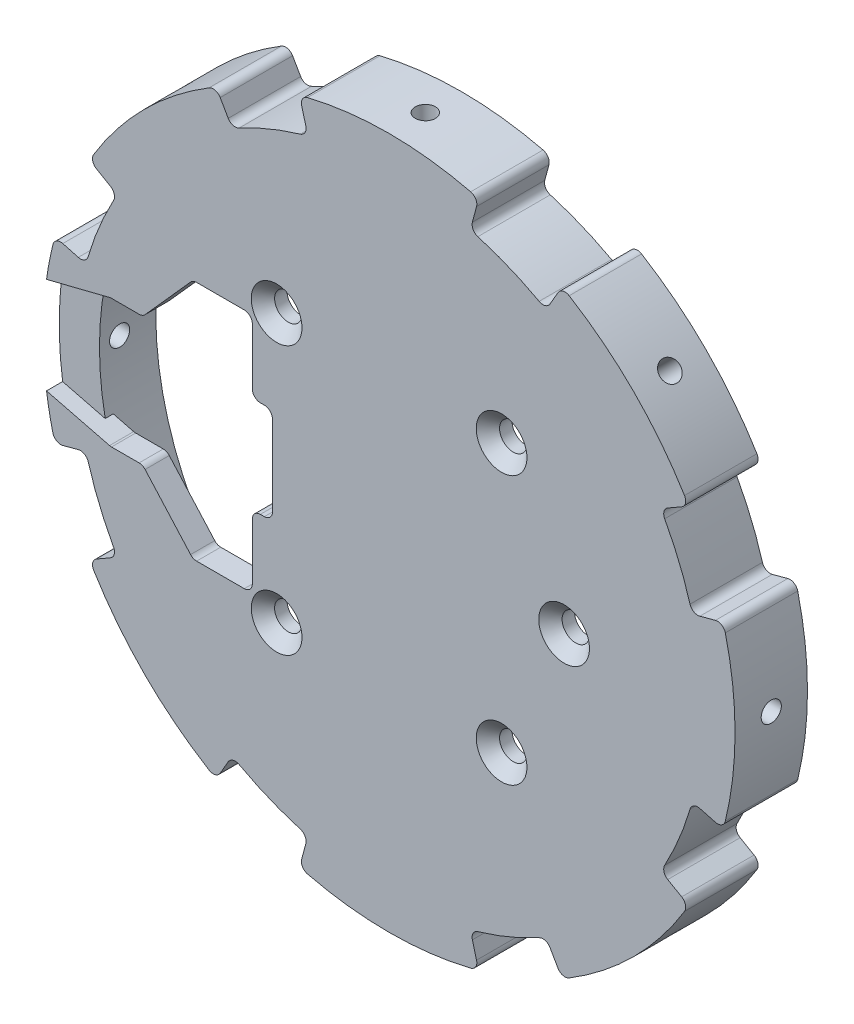
SolidWorks part; units mm, degrees
ref_plane "前视基准面" through (0, 0, 0) normal (0, 0, 1) x (1, 0, 0)
ref_plane "上视基准面" through (0, 0, 0) normal (0, 1, 0) x (1, 0, 0)
ref_plane "右视基准面" through (0, 0, 0) normal (1, 0, 0) x (0, 0, -1)
sketch "草图1" plane through (0, 0, 0) normal (0, 0, 1) x (1, 0, 0)
  line L16 (21.5, 37.2391) -> (19.5, 33.775)
  line L17 (11.1292, 41.5348) -> (10.0939, 37.6711)
  line L18 (-11.1292, 41.5348) -> (-10.0939, 37.6711)
  line L19 (37.2391, 21.5) -> (33.775, 19.5)
  line L20 (41.5348, 11.1292) -> (37.6711, 10.0939)
  line L21 (41.5348, -11.1292) -> (37.6711, -10.0939)
  line L22 (37.2391, -21.5) -> (33.775, -19.5)
  line L23 (21.5, -37.2391) -> (19.5, -33.775)
  line L24 (11.1292, -41.5348) -> (10.0939, -37.6711)
  line L25 (-11.1292, -41.5348) -> (-10.0939, -37.6711)
  line L26 (-21.5, -37.2391) -> (-19.5, -33.775)
  line L27 (-37.2391, -21.5) -> (-33.775, -19.5)
  line L28 (-41.5348, -11.1292) -> (-37.6711, -10.0939)
  line L29 (-41.5348, 11.1292) -> (-37.6711, 10.0939)
  line L30 (-37.2391, 21.5) -> (-33.775, 19.5)
  line L31 (-21.5, 37.2391) -> (-19.5, 33.775)
  circle A1 centre (0, 0) radius 38
  arc A6 (0, 43) -> (-11.1292, 41.5348) centre (0, 0) ccw
  arc A31 (0, 43) -> (11.1292, 41.5348) centre (0, 0) cw
  arc A32 (10.0939, 37.6711) -> (19.5, 33.775) centre (0, 0) cw
  arc A33 (30.4056, 30.4056) -> (21.5, 37.2391) centre (0, 0) ccw
  arc A34 (30.4056, 30.4056) -> (37.2391, 21.5) centre (0, 0) cw
  arc A35 (33.775, 19.5) -> (37.6711, 10.0939) centre (0, 0) cw
  arc A36 (43, 0) -> (41.5348, 11.1292) centre (0, 0) ccw
  arc A37 (43, 0) -> (41.5348, -11.1292) centre (0, 0) cw
  arc A38 (37.6711, -10.0939) -> (33.775, -19.5) centre (0, 0) cw
  arc A39 (30.4056, -30.4056) -> (37.2391, -21.5) centre (0, 0) ccw
  arc A40 (30.4056, -30.4056) -> (21.5, -37.2391) centre (0, 0) cw
  arc A41 (19.5, -33.775) -> (10.0939, -37.6711) centre (0, 0) cw
  arc A42 (0, -43) -> (11.1292, -41.5348) centre (0, 0) ccw
  arc A43 (0, -43) -> (-11.1292, -41.5348) centre (0, 0) cw
  arc A44 (-10.0939, -37.6711) -> (-19.5, -33.775) centre (0, 0) cw
  arc A45 (-30.4056, -30.4056) -> (-21.5, -37.2391) centre (0, 0) ccw
  arc A46 (-30.4056, -30.4056) -> (-37.2391, -21.5) centre (0, 0) cw
  arc A47 (-33.775, -19.5) -> (-37.6711, -10.0939) centre (0, 0) cw
  arc A48 (-43, 0) -> (-41.5348, -11.1292) centre (0, 0) ccw
  arc A49 (-43, 0) -> (-41.5348, 11.1292) centre (0, 0) cw
  arc A50 (-37.6711, 10.0939) -> (-33.775, 19.5) centre (0, 0) cw
  arc A51 (-30.4056, 30.4056) -> (-37.2391, 21.5) centre (0, 0) ccw
  arc A52 (-30.4056, 30.4056) -> (-21.5, 37.2391) centre (0, 0) cw
  arc A53 (-19.5, 33.775) -> (-10.0939, 37.6711) centre (0, 0) cw
  point P55 (0, 0)
  point P56 (0, 0)
  dimension "D1" = 8
extrude "凸台-拉伸1" add sketch "草图1" against normal blind 6
sketch "草图2" plane through (0, 0, 0) normal (0, 0, 1) x (1, 0, 0)
  line L16 (-11.1292, 41.5348) -> (-10.0939, 37.6711)
  line L17 (10.0939, 37.6711) -> (11.1292, 41.5348)
  line L18 (21.5, 37.2391) -> (19.5, 33.775)
  line L19 (33.775, 19.5) -> (37.2391, 21.5)
  line L20 (41.5348, 11.1292) -> (37.6711, 10.0939)
  line L21 (37.6711, -10.0939) -> (41.5348, -11.1292)
  line L22 (37.2391, -21.5) -> (33.775, -19.5)
  line L23 (19.5, -33.775) -> (21.5, -37.2391)
  line L24 (11.1292, -41.5348) -> (10.0939, -37.6711)
  line L25 (-10.0939, -37.6711) -> (-11.1292, -41.5348)
  line L26 (-21.5, -37.2391) -> (-19.5, -33.775)
  line L27 (-33.775, -19.5) -> (-37.2391, -21.5)
  line L28 (-41.5348, -11.1292) -> (-37.6711, -10.0939)
  line L29 (-37.6711, 10.0939) -> (-41.5348, 11.1292)
  line L30 (-37.2391, 21.5) -> (-33.775, 19.5)
  line L31 (-19.5, 33.775) -> (-21.5, 37.2391)
  arc A27 (0, 43) -> (11.1292, 41.5348) centre (0, 0) cw
  arc A28 (10.0939, 37.6711) -> (19.5, 33.775) centre (0, 0) cw
  arc A29 (0, 43) -> (-11.1292, 41.5348) centre (0, 0) ccw
  arc A30 (30.4056, 30.4056) -> (21.5, 37.2391) centre (0, 0) ccw
  arc A31 (30.4056, 30.4056) -> (37.2391, 21.5) centre (0, 0) cw
  arc A32 (33.775, 19.5) -> (37.6711, 10.0939) centre (0, 0) cw
  arc A33 (43, 0) -> (41.5348, 11.1292) centre (0, 0) ccw
  arc A34 (43, 0) -> (41.5348, -11.1292) centre (0, 0) cw
  arc A35 (37.6711, -10.0939) -> (33.775, -19.5) centre (0, 0) cw
  arc A36 (30.4056, -30.4056) -> (37.2391, -21.5) centre (0, 0) ccw
  arc A37 (30.4056, -30.4056) -> (21.5, -37.2391) centre (0, 0) cw
  arc A38 (19.5, -33.775) -> (10.0939, -37.6711) centre (0, 0) cw
  arc A39 (0, -43) -> (11.1292, -41.5348) centre (0, 0) ccw
  arc A40 (0, -43) -> (-11.1292, -41.5348) centre (0, 0) cw
  arc A41 (-10.0939, -37.6711) -> (-19.5, -33.775) centre (0, 0) cw
  arc A42 (-30.4056, -30.4056) -> (-21.5, -37.2391) centre (0, 0) ccw
  arc A43 (-30.4056, -30.4056) -> (-37.2391, -21.5) centre (0, 0) cw
  arc A44 (-33.775, -19.5) -> (-37.6711, -10.0939) centre (0, 0) cw
  arc A45 (-43, 0) -> (-41.5348, -11.1292) centre (0, 0) ccw
  arc A46 (-43, 0) -> (-41.5348, 11.1292) centre (0, 0) cw
  arc A47 (-37.6711, 10.0939) -> (-33.775, 19.5) centre (0, 0) cw
  arc A48 (-30.4056, 30.4056) -> (-37.2391, 21.5) centre (0, 0) ccw
  arc A49 (-30.4056, 30.4056) -> (-21.5, 37.2391) centre (0, 0) cw
  arc A50 (-19.5, 33.775) -> (-10.0939, 37.6711) centre (0, 0) cw
  point P43 (0, 0)
extrude "凸台-拉伸2" add sketch "草图2" along normal blind 3
hole_wizard "M3 锥坑平头的锥孔1" positions "3D草图2" profile "草图4" countersink size "M3" standard "BSI" end condition through all
sketch3d "3D草图2"
  point P25 (13.9806, -16.6615, 3)
  point P27 (21.75, 0, 3)
  point P40 (13.9806, 16.6615, 3)
  point P41 (-13.9806, -16.6615, 3)
  point P42 (-21.75, 0, 3)
  point P43 (-13.9806, 16.6615, 3)
sketch "草图4" plane through (13.9806, -16.6615, 3) normal (1, 0, 0) x (0, -1, 0)
  line L0 (0, 0) -> (0, 9)
  line L1 (0, 9) -> (1.7, 9)
  line L2 (1.7, 9) -> (1.7, 1.45)
  line L3 (1.7, 1.45) -> (3.15, 0)
  line L5 (3.15, 0) -> (0, 0)
  line L6 (-1.7, 1.45) -> (-3.15, 0) construction
  line L11 (0, -6.35) -> (0, 107.95) construction
  dimension "通孔孔直径" = 3.4
  dimension "通孔孔深度" = 9
  dimension "近端锥形沉头孔直径" = 6.3
  dimension "近端锥形沉头孔角度" = 90
hole_wizard "M3x0.5 螺纹孔1" positions "3D草图3" profile "草图5" tap size "M3x0.5" standard "BSI" end condition up to next
sketch3d "3D草图3"
  point P5 (0, -43, -1.5)
  point P13 (30.4056, -30.4056, -1.5)
  point P33 (30.4056, 30.4056, -1.5)
  point P43 (43, 0, -1.5)
  point P53 (-30.4056, 30.4056, -1.5)
  point P55 (-30.4056, -30.4056, -1.5)
  point P57 (43, 0, -1.5)
  point P72 (-43, 0, -1.5)
  point P77 (0, 43, -1.5)
sketch "草图5" plane through (0, -43, -1.5) normal (1, 0, 0) x (0, 0, -1)
  line L0 (0, 0) -> (0, 5)
  line L1 (0, 5) -> (1.25, 5)
  line L2 (1.25, 5) -> (1.25, 0)
  line L5 (1.25, 0) -> (0, 0)
  line L11 (0, -6.35) -> (0, 107.95) construction
  dimension "通孔螺纹孔钻头直径" = 2.5
  dimension "通孔螺纹孔钻头深度" = 5
cosmetic thread "孔螺蚊线1" parameters "D2"=3
cosmetic thread "孔螺蚊线2" parameters "D2"=3
cosmetic thread "孔螺蚊线3" parameters "D2"=3
cosmetic thread "孔螺蚊线4" parameters "D2"=3
cosmetic thread "孔螺蚊线5" parameters "D2"=3
cosmetic thread "孔螺蚊线6" parameters "D2"=3
sketch "草图6" plane through (0, 0, 0) normal (0, 0, 1) x (1, 0, 0)
  line L3 (-14.5, -6) -> (-14.5, 6)
  line L4 (-14.5, 6) -> (-17, 6)
  line L13 (-14.5, -6) -> (-17, -6)
  line L21 (-17, -15) -> (-17, -6)
  line L22 (-42.5793, 6) -> (-34.6246, 8)
  line L23 (-42.5793, -6) -> (-34.6246, -8)
  line L24 (-17, 6) -> (-17, 15)
  line L25 (-34.6246, 8) -> (-30.6246, 8)
  line L26 (-17, 15) -> (-24.3746, 15)
  line L27 (-30.6246, 8) -> (-24.3746, 15)
  line L28 (-34.6246, -8) -> (-30.6246, -8)
  line L29 (-30.6246, -8) -> (-24.3746, -15)
  line L30 (-24.3746, -15) -> (-17, -15)
  arc A2 (-41.5348, 11.1292) -> (-41.5348, -11.1292) centre (0, 0) ccw construction
  arc A3 (-42.5793, 6) -> (-42.5793, -6) centre (0, 0) ccw
extrude "切除-拉伸1" cut sketch "草图6" along normal blind 3
sketch "草图9" plane through (0, 0, 0) normal (0, 0, 1) x (1, 0, 0)
  line L0 (-34.6246, 8) -> (-42.5793, 6) construction
  line L1 (-37.2862, 7.3308) -> (-42.5793, 6) construction
  line L2 (-42.5793, 6) -> (-37.2862, 7.3308)
  line L3 (-42.5793, -6) -> (-37.2862, -7.3308)
  arc A0 (-37.2862, -7.3308) -> (-37.2862, 7.3308) centre (0, 0) cw
  arc A1 (-42.5793, -6) -> (-42.5793, 6) centre (0, 0) cw
extrude "凸台-拉伸3" add sketch "草图9" along normal blind 1
fillet "圆角1" radius 1 32 edges at (-21.5, 37.2391, -1.5) (-37.6711, 10.0939, -1.5) (-37.2391, 21.5, -1.5) (-33.775, 19.5, -1.5) (-41.5348, 11.1292, -1.5) (-37.2391, -21.5, -1.5) (-33.775, -19.5, -1.5) (-37.6711, -10.0939, -1.5) (-41.5348, -11.1292, -1.5) (-21.5, -37.2391, -1.5) (-19.5, -33.775, -1.5) (-11.1292, -41.5348, -1.5) (-10.0939, -37.6711, -1.5) (21.5, -37.2391, -1.5) (11.1292, -41.5348, -1.5) (10.0939, -37.6711, -1.5) (19.5, -33.775, -1.5) (37.2391, -21.5, -1.5) (33.775, -19.5, -1.5) (37.6711, 10.0939, -1.5) (37.6711, -10.0939, -1.5) (41.5348, -11.1292, -1.5) (41.5348, 11.1292, -1.5) (33.775, 19.5, -1.5) (37.2391, 21.5, -1.5) (10.0939, 37.6711, -1.5) (21.5, 37.2391, -1.5) (19.5, 33.775, -1.5) (11.1292, 41.5348, -1.5) (-10.0939, 37.6711, -1.5) (-11.1292, 41.5348, -1.5) (-19.5, 33.775, -1.5)
fillet "圆角2" radius 1 12 edges at (-24.3746, -15, 1.5) (-34.6246, -8, 1.5) (-30.6246, -8, 1.5) (-17, -15, 1.5) (-14.5, -6, 1.5) (-17, 15, 1.5) (-30.6246, 8, 1.5) (-17, -6, 1.5) (-14.5, 6, 1.5) (-17, 6, 1.5) (-24.3746, 15, 1.5) (-34.6246, 8, 1.5)
